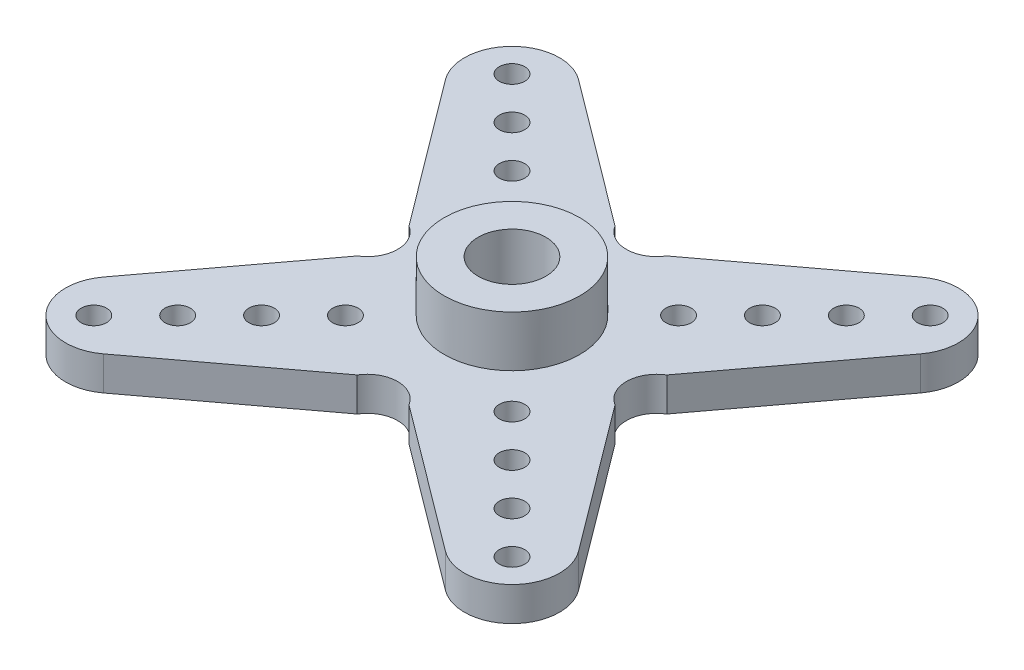
SolidWorks part; units mm, degrees
ref_plane "Front Plane" through (0, 0, 0) normal (0, 0, 1) x (1, 0, 0)
ref_plane "Top Plane" through (0, 0, 0) normal (0, 1, 0) x (1, 0, 0)
ref_plane "Right Plane" through (0, 0, 0) normal (1, 0, 0) x (0, 0, -1)
sketch "Sketch1" plane through (0, 0, 0) normal (0, 1, 0) x (1, 0, 0)
  line L1 (-16.5732, 5.6349) -> (10.9332, 5.6349) construction
  line L2 (-2.82, 5.6349) -> (-2.82, -21.8715) construction
  line L3 (10.9332, -21.8715) -> (-16.5732, -21.8715) construction
  line L4 (10.9332, 5.6349) -> (10.9332, -21.8715) construction
  line L5 (-10.4267, -6.5927) -> (-4.3456, -0.5116) construction
  line L6 (-16.5732, 5.6349) -> (10.9332, -21.8715) construction
  line L7 (-16.2904, -8.1183) -> (10.9332, -8.1183) construction
  line L8 (11.1955, 1.9694) -> (4.7867, -6.5927)
  line L9 (7.2676, 5.8972) -> (-1.2945, -0.5116)
  line L10 (4.7867, -6.5927) -> (-1.2945, -0.5116) construction
  line L11 (-16.8355, -18.2059) -> (-10.4267, -9.6438)
  line L12 (-12.9077, -22.1338) -> (-4.3456, -15.725)
  line L13 (-12.9077, 5.8972) -> (-4.3456, -0.5116)
  line L14 (-16.8355, 1.9694) -> (-10.4267, -6.5927)
  line L15 (-16.5732, -21.8715) -> (10.9332, 5.6349) construction
  line L19 (7.2676, -22.1338) -> (-1.2945, -15.725)
  line L20 (11.1955, -18.2059) -> (4.7867, -9.6438)
  circle A0 centre (-2.82, -8.1183) radius 6.75 construction
  arc A1 (-10.4267, -6.5927) -> (-10.4267, -9.6438) centre (-11.3567, -8.1183) cw
  arc A2 (11.1955, -18.2059) -> (7.2676, -22.1338) centre (8.9491, -19.8874) cw
  arc A3 (-16.8355, 1.9694) -> (-12.9077, 5.8972) centre (-14.5891, 3.6508) cw
  arc A4 (11.1955, 1.9694) -> (7.2676, 5.8972) centre (8.9491, 3.6508) ccw
  arc A5 (4.7867, -6.5927) -> (4.7867, -9.6438) centre (5.7167, -8.1183) ccw
  arc A6 (-16.8355, -18.2059) -> (-12.9077, -22.1338) centre (-14.5891, -19.8874) ccw
  arc A7 (-1.2945, -15.725) -> (-4.3456, -15.725) centre (-2.82, -16.655) ccw
  arc A8 (-1.2945, -0.5116) -> (-4.3456, -0.5116) centre (-2.82, 0.4184) cw
  point P6 (10.9332, -8.1183)
  point P7 (-2.82, 5.6349)
  dimension "D2" = 2.806
  dimension "D3" = 1.7867
  dimension "D1" = 19.45
  dimension "D4" = 8.6
extrude "Boss-Extrude1" add sketch "Sketch1" along normal blind 2
sketch "Sketch5" plane through (0, 2, 0) normal (0, 1, 0) x (1, 0, 0)
  circle A4 centre (-2.82, -8.1183) radius 4
  circle A5 centre (-2.82, -8.1183) radius 1.9985
  circle A6 centre (-2.82, -8.1183) radius 6.75 construction
  dimension "D1" = 8
extrude "Boss-Extrude2" add sketch "Sketch5" along normal blind 3
ref_axis "Axis1" through (-2.82, 5, 8.1183) along (0, -1, 0)
sketch "Sketch8" plane through (0, 0, 0) normal (0, -1, 0) x (1, 0, 0)
  circle A0 centre (-2.82, 8.1183) radius 1.5
  dimension "D1" = 3
extrude "Cut-Extrude2" cut sketch "Sketch8" against normal through all
sketch "Sketch9" plane through (0, 0, 0) normal (0, -1, 0) x (1, 0, 0)
  circle A0 centre (-2.82, 8.1183) radius 3.6
  circle A1 centre (-2.82, 8.1183) radius 3
  dimension "D1" = 7.2
  dimension "D2" = 0.6
sketch "Sketch10" plane through (0, 0, 0) normal (0, -1, 0) x (1, 0, 0)
  line L0 (-16.5732, 21.8715) -> (10.9332, -5.6349) construction
  circle A0 centre (9.519, -4.2207) radius 0.75
  dimension "D1" = 1.5
  dimension "D2" = 2
extrude "Cut-Extrude3" cut sketch "Sketch10" against normal up to next
pattern_linear "LPattern1" count 4 spacing 3.5 along (-0.7071, 0, 0.7071) of "Cut-Extrude3"
pattern_circular "CirPattern1" count 4 every 90 about axis through (-2.82, 5, 8.1183) along (0, -1, 0) of "LPattern1"
sketch "Sketch11" plane through (0, 2, 0) normal (0, 1, 0) x (1, 0, 0)
  line L0 (-10.5782, -8.1183) -> (-22.2828, 5.101)
  line L1 (-22.2828, 5.101) -> (-13.4943, 7.8108)
  line L2 (-13.4943, 7.8108) -> (-1.7398, 1.9152)
  line L3 (-1.7398, 1.9152) -> (-2.5032, -0.3666)
  arc A0 (-10.5782, -8.1183) -> (-2.5032, -0.3666) centre (-2.82, -8.1183) ccw
extrude "Cut-Extrude4" [suppressed] cut sketch "Sketch11" against normal through all both and the other way through all flip side to cut
sketch "Sketch13" plane through (0, 0, 0) normal (0, -1, 0) x (1, 0, 0)
  line L0 (-2.82, 8.1183) -> (-17.7079, -6.7696) construction
  arc A0 (-16.8355, -1.9694) -> (-12.9077, -5.8972) centre (-14.5891, -3.6508) ccw construction
  point P6 (-16.5732, -5.6349)
